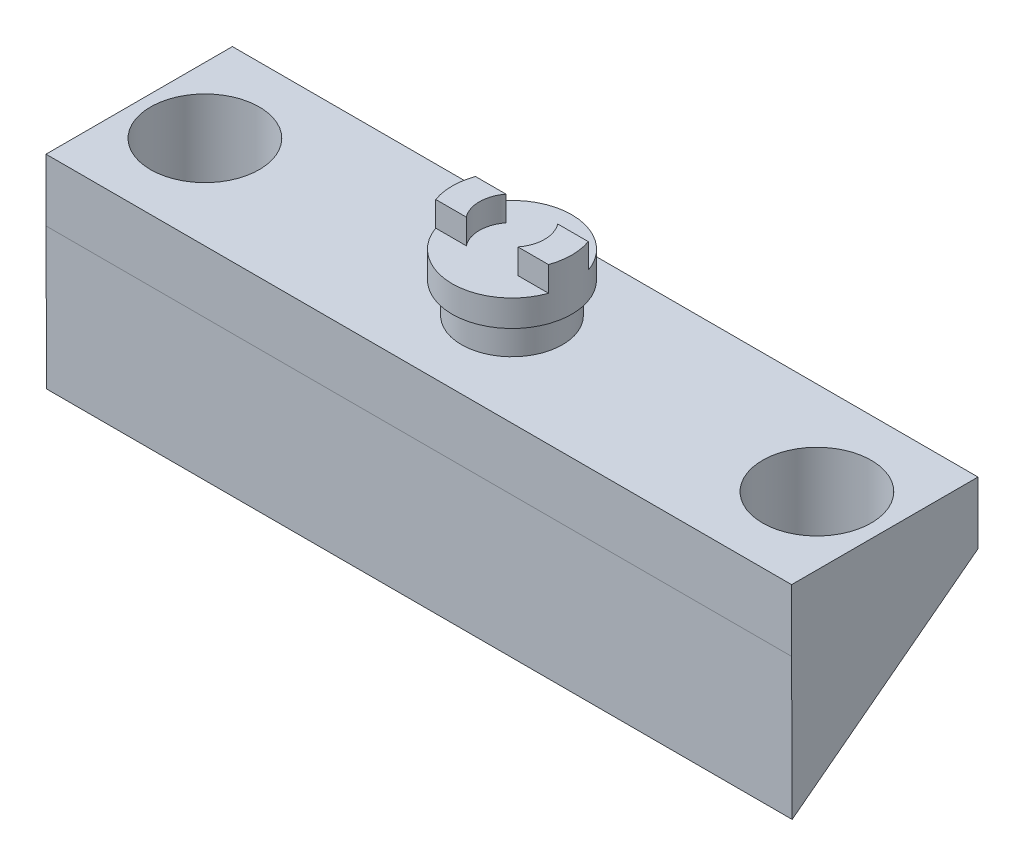
SolidWorks part; units mm, degrees
ref_plane "Front Plane" through (0, 0, 0) normal (0, 0, 1) x (1, 0, 0)
ref_plane "Top Plane" through (0, 0, 0) normal (0, 1, 0) x (1, 0, 0)
ref_plane "Right Plane" through (0, 0, 0) normal (1, 0, 0) x (0, 0, -1)
sketch "Sketch1" plane through (0, 0, 0) normal (0, 1, 0) x (1, 0, 0)
  line L1 (-42.7558, 11.9638) -> (5.2442, 11.9638)
  line L2 (-42.7558, 11.9638) -> (-42.7558, -0.0362)
  line L3 (-42.7558, -0.0362) -> (5.2442, -0.0362)
  line L4 (5.2442, 11.9638) -> (5.2442, -0.0362)
  circle A0 centre (-38.5258, 5.9638) radius 2
  circle A1 centre (0.8742, 5.9638) radius 2
  point P10 (-33.8349, 8.0836)
  dimension "D3" = 4
  dimension "D5" = 4
  dimension "D1" = 48
  dimension "D2" = 12
  dimension "D4" = 4.23
  dimension "D6" = 39.4
extrude "Boss-Extrude2" add sketch "Sketch1" along normal blind 4
sketch "Sketch2" plane through (0, 4, 0) normal (0, 1, 0) x (1, 0, 0)
  circle A0 centre (0.8742, 5.9638) radius 3.5
  circle A1 centre (-38.5258, 5.9638) radius 3.5
  dimension "D1" = 7
  dimension "D2" = 7
extrude "Cut-Extrude5" cut sketch "Sketch2" against normal through all
sketch "Sketch3" plane through (0, 4, 0) normal (0, 1, 0) x (1, 0, 0)
  line L0 (5.2442, -0.0362) -> (5.2442, 11.9638) construction
  circle A0 centre (-18.7558, 5.9638) radius 3.25
  point P2 (5.2442, 5.9638)
  dimension "D1" = 6.5
  dimension "D2" = 24
extrude "Boss-Extrude3" add sketch "Sketch3" along normal blind 2
sketch "Sketch4" plane through (0, 6, 0) normal (0, 1, 0) x (1, 0, 0)
  circle A0 centre (-18.7558, 5.9638) radius 3.85
  point P3 (-14.1972, 4.9238)
  dimension "D1" = 7.7
extrude "Boss-Extrude4" add sketch "Sketch4" along normal blind 3.3
sketch "Sketch5" plane through (0, 9.3, 0) normal (0, 1, 0) x (1, 0, 0)
  line L0 (-18.7558, 5.9638) -> (49981.2442, 5.9638) construction
  line L2 (-24.1568, 1.5798) -> (-13.4122, 1.5798)
  line L3 (-24.1568, 1.5798) -> (-24.1568, 4.6838)
  line L4 (-24.1568, 4.6838) -> (-13.4122, 4.6838)
  line L5 (-13.4122, 1.5798) -> (-13.4122, 4.6838)
  line L6 (-24.7026, 7.2438) -> (-12.6618, 7.2438)
  line L7 (-24.7026, 7.2438) -> (-24.7026, 11.951)
  line L8 (-24.7026, 11.951) -> (-12.6618, 11.951)
  line L9 (-12.6618, 7.2438) -> (-12.6618, 11.951)
  dimension "D1" = 1.28
  dimension "D2" = 1.28
extrude "Cut-Extrude6" cut sketch "Sketch5" against normal blind 1.6
sketch "Sketch6" plane through (0, 9.3, 0) normal (0, 1, 0) x (1, 0, 0)
  circle A0 centre (-18.7558, 5.9638) radius 2.1
  dimension "D1" = 4.2
extrude "Cut-Extrude7" cut sketch "Sketch6" against normal blind 1.6
sketch "Sketch7" plane through (5.2442, 0, 0) normal (1, 0, 0) x (0, 0, -1)
  line L0 (11.9638, 0) -> (0, -9.1098)
  line L1 (0, -9.1098) -> (-0.0362, 0)
  line L2 (-0.0362, 0) -> (11.9638, 0)
extrude "Boss-Extrude5" add sketch "Sketch7" against normal blind 48
sketch "Sketch8" plane through (0, 0, 0) normal (0, 1, 0) x (1, 0, 0)
  circle A0 centre (0.8742, 5.9638) radius 2
extrude "Cut-Extrude8" cut sketch "Sketch8" against normal through all
sketch "Sketch9" plane through (0, 0, 0) normal (0, 1, 0) x (1, 0, 0)
  circle A0 centre (-38.5258, 5.9638) radius 2
extrude "Cut-Extrude9" cut sketch "Sketch9" against normal through all
sketch "Sketch10" plane through (0, 0, 0) normal (0, 1, 0) x (1, 0, 0)
  circle A0 centre (0.8742, 5.9638) radius 3.5
  circle A1 centre (-38.5258, 5.9638) radius 3.5
extrude "Cut-Extrude10" cut sketch "Sketch10" against normal blind 1
